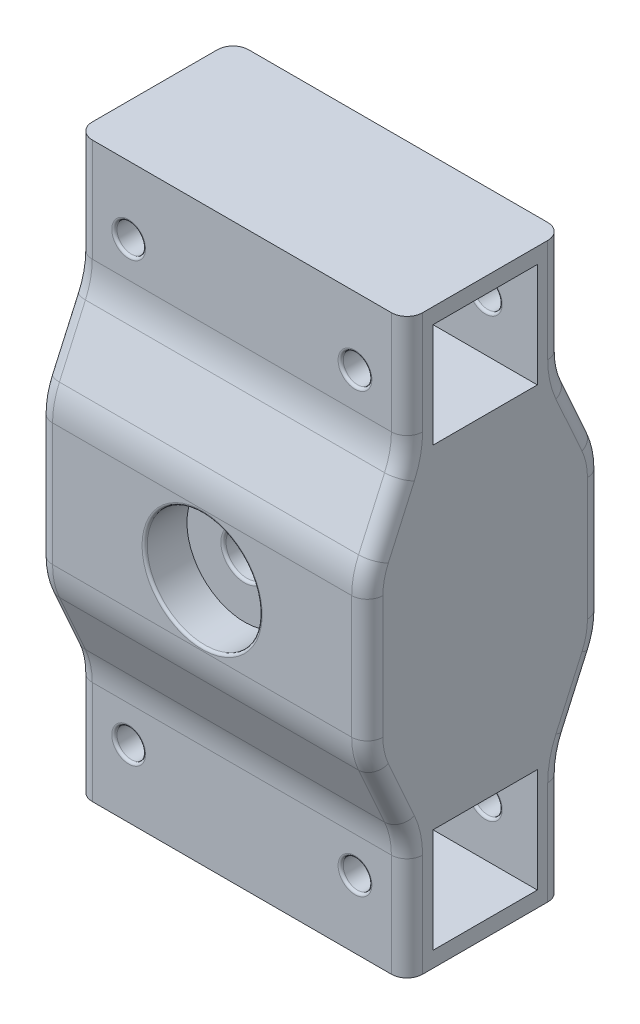
SolidWorks part; units mm, degrees
ref_plane "Front Plane" through (0, 0, 0) normal (0, 0, 1) x (1, 0, 0)
ref_plane "Top Plane" through (0, 0, 0) normal (0, 1, 0) x (1, 0, 0)
ref_plane "Right Plane" through (0, 0, 0) normal (1, 0, 0) x (0, 0, -1)
sketch "Sketch1" plane through (0, 0, 0) normal (1, 0, 0) x (0, 0, -1)
  line L0 (-15.025, 32.02) -> (-22.6575, 15)
  line L1 (0, 0) -> (50000, 0) construction
  line L3 (-10.025, 52.07) -> (-10.025, 32.02)
  line L6 (-10.025, 32.02) -> (10.025, 32.02)
  line L7 (-10.025, 52.07) -> (-15.025, 52.07)
  line L8 (-15.025, 52.07) -> (-15.025, 32.02)
  line L20 (-22.6575, 15) -> (-22.6575, -15)
  line L28 (0, 0) -> (0, 50000) construction
  line L29 (22.6575, 15) -> (22.6575, -15)
  line L30 (15.025, 52.07) -> (15.025, 32.02)
  line L31 (10.025, 52.07) -> (15.025, 52.07)
  line L32 (10.025, 52.07) -> (10.025, 32.02)
  line L33 (15.025, 32.02) -> (22.6575, 15)
  line L34 (15.025, -32.02) -> (22.6575, -15)
  line L35 (10.025, -52.07) -> (10.025, -32.02)
  line L36 (10.025, -52.07) -> (15.025, -52.07)
  line L37 (15.025, -52.07) -> (15.025, -32.02)
  line L38 (-15.025, -52.07) -> (-15.025, -32.02)
  line L39 (-10.025, -52.07) -> (-15.025, -52.07)
  line L40 (-10.025, -32.02) -> (10.025, -32.02)
  line L41 (-10.025, -52.07) -> (-10.025, -32.02)
  line L42 (-15.025, -32.02) -> (-22.6575, -15)
  point P17 (0, 32.02)
  point P22 (22.6575, 0)
  point P23 (-22.6575, 0)
  point P27 (0, -32.02)
  dimension "D5" = 20.05
  dimension "D6" = 52.07
  dimension "D1" = 10.025
  dimension "D2" = 15
  dimension "D3" = 5
extrude "Boss-Extrude1" add sketch "Sketch1" along normal mid plane 63.5
sketch "Sketch2" plane through (0, 0, 15.025) normal (0, 0, 1) x (1, 0, 0)
  line L1 (31.75, 52.07) -> (-31.75, 52.07) construction
  line L2 (-31.75, 52.07) -> (-31.75, 32.02) construction
  line L3 (0, 0) -> (0, 19.2106) construction
  circle A5 centre (-21.75, 42.07) radius 2.75
  circle A6 centre (21.75, 42.07) radius 2.75
  dimension "D2" = 10
  dimension "D1" = 5.5
  dimension "D3" = 10
extrude "Cut-Extrude1" cut sketch "Sketch2" against normal through all
mirror "Mirror1" about plane through (0, 0, 0) normal (0, 1, 0) of "Cut-Extrude1"
sketch "Sketch3" plane through (0, 0, 22.6575) normal (0, 0, 1) x (1, 0, 0)
  circle A0 centre (0, 0) radius 11.049
  dimension "D1" = 22.098
extrude "Cut-Extrude2" cut sketch "Sketch3" against normal through all
fillet "Fillet1" radius 0.5 15 edges at (-21.75, 44.82, -10.025) (24.5, 42.07, -15.025) (21.75, 44.82, -10.025) (21.75, 39.32, 10.025) (19, 42.07, 15.025) (-21.75, 39.32, 10.025) (-19, 42.07, 15.025) (21.75, -39.32, -10.025) (24.5, -42.07, -15.025) (-21.75, -39.32, -10.025) (-19, -42.07, -15.025) (21.75, -44.82, 10.025) (19, -42.07, 15.025) (-21.75, -44.82, 10.025) (-19, -42.07, 15.025)
fillet "Fillet2" radius 15 8 edges at (0, 32.02, -15.025) (0, 15, -22.6575) (0, -15, -22.6575) (0, -32.02, -15.025) (0, -32.02, 15.025) (0, -15, 22.6575) (0, 15, 22.6575) (0, 32.02, 15.025)
fillet "Fillet3" radius 3 36 edges at (-31.75, 32.091, -15.357) (-31.75, 32.091, 15.357) (-31.75, 23.51, 18.8412) (-31.75, 14.929, 22.3255) (-31.75, 0, 22.6575) (-31.75, -14.929, 22.3255) (-31.75, -23.51, 18.8412) (-31.75, -32.091, 15.357) (-31.75, -32.091, -15.357) (-31.75, -23.51, -18.8412) (-31.75, -14.929, -22.3255) (-31.75, 0, -22.6575) (-31.75, 14.929, -22.3255) (-31.75, 23.51, -18.8412) (31.75, -14.929, -22.3255) (31.75, -23.51, -18.8412) (31.75, -32.091, -15.357) (31.75, -32.091, 15.357) (31.75, -23.51, 18.8412) (31.75, -14.929, 22.3255) (31.75, 0, 22.6575) (31.75, 14.929, 22.3255) (31.75, 23.51, 18.8412) (31.75, 32.091, 15.357) (31.75, 32.091, -15.357) (31.75, 23.51, -18.8412) (31.75, 14.929, -22.3255) (31.75, 0, -22.6575) (-31.75, 43.6497, 15.025) (-31.75, -43.6497, 15.025) (-31.75, -43.6497, -15.025) (-31.75, 43.6497, -15.025) (31.75, 43.6497, 15.025) (31.75, -43.6497, 15.025) (31.75, -43.6497, -15.025) (31.75, 43.6497, -15.025)
sketch "Sketch4" plane through (0, 0, 0) normal (0, 0, 1) x (1, 0, 0)
  circle A0 centre (0, 0) radius 11.049 construction
  circle A1 centre (0, 0) radius 11.049
  circle A2 centre (0, 0) radius 4.025
  dimension "D1" = 8.05
extrude "Boss-Extrude2" add sketch "Sketch4" along normal offset from surface (14.5295 mm away) 8.128 up to face at (11.049, 0, 22.6575)
sketch "Sketch5" plane through (0, 0, 0) normal (0, 0, -1) x (-1, 0, 0)
  circle A0 centre (0, 0) radius 4.025 construction
  circle A1 centre (0, 0) radius 11.049
  circle A2 centre (0, 0) radius 11.049
  circle A3 centre (0, 0) radius 4.025
  dimension "D1" = 0
extrude "Boss-Extrude3" add sketch "Sketch5" along normal offset from surface (14.5295 mm away) 8.128 up to face at (11.049, 0, -22.6575)
fillet "Fillet5" radius 0.5 4 edges at (4.025, 0, -14.5295) (-4.025, 0, 14.5295) (11.049, 0, -22.6575) (11.049, 0, 22.6575)
sketch "Sketch6" plane through (0, 52.07, 0) normal (0, 1, 0) x (1, 0, 0)
  line L0 (-31.75, 10.025) -> (-31.75, -10.025) construction
  line L2 (31.75, -10.025) -> (31.75, 10.025) construction
  line L4 (-31.75, -10.025) -> (-31.75, -12.025) construction
  line L5 (-28.75, -15.025) -> (28.75, -15.025) construction
  line L6 (31.75, -12.025) -> (31.75, -10.025) construction
  line L8 (28.75, 15.025) -> (-28.75, 15.025) construction
  line L9 (-31.75, 12.025) -> (-31.75, 10.025) construction
  line L11 (31.75, 10.025) -> (31.75, 12.025) construction
  line L12 (-31.75, 10.025) -> (-31.75, -10.025)
  line L14 (31.75, -10.025) -> (31.75, 10.025)
  line L16 (-31.75, -10.025) -> (-31.75, -12.025)
  line L17 (-28.75, -15.025) -> (28.75, -15.025)
  line L18 (31.75, -12.025) -> (31.75, -10.025)
  line L20 (28.75, 15.025) -> (-28.75, 15.025)
  line L21 (-31.75, 12.025) -> (-31.75, 10.025)
  line L23 (31.75, 10.025) -> (31.75, 12.025)
  arc A0 (-31.75, -12.025) -> (-28.75, -15.025) centre (-28.75, -12.025) ccw construction
  arc A1 (28.75, -15.025) -> (31.75, -12.025) centre (28.75, -12.025) ccw construction
  arc A2 (-28.75, 15.025) -> (-31.75, 12.025) centre (-28.75, 12.025) ccw construction
  arc A3 (31.75, 12.025) -> (28.75, 15.025) centre (28.75, 12.025) ccw construction
  arc A4 (-31.75, -12.025) -> (-28.75, -15.025) centre (-28.75, -12.025) ccw
  arc A5 (28.75, -15.025) -> (31.75, -12.025) centre (28.75, -12.025) ccw
  arc A6 (-28.75, 15.025) -> (-31.75, 12.025) centre (-28.75, 12.025) ccw
  arc A7 (31.75, 12.025) -> (28.75, 15.025) centre (28.75, 12.025) ccw
extrude "Boss-Extrude4" add sketch "Sketch6" along normal blind 3
mirror "Mirror2" about plane through (0, 0, 0) normal (0, 1, 0) of "Boss-Extrude4"
